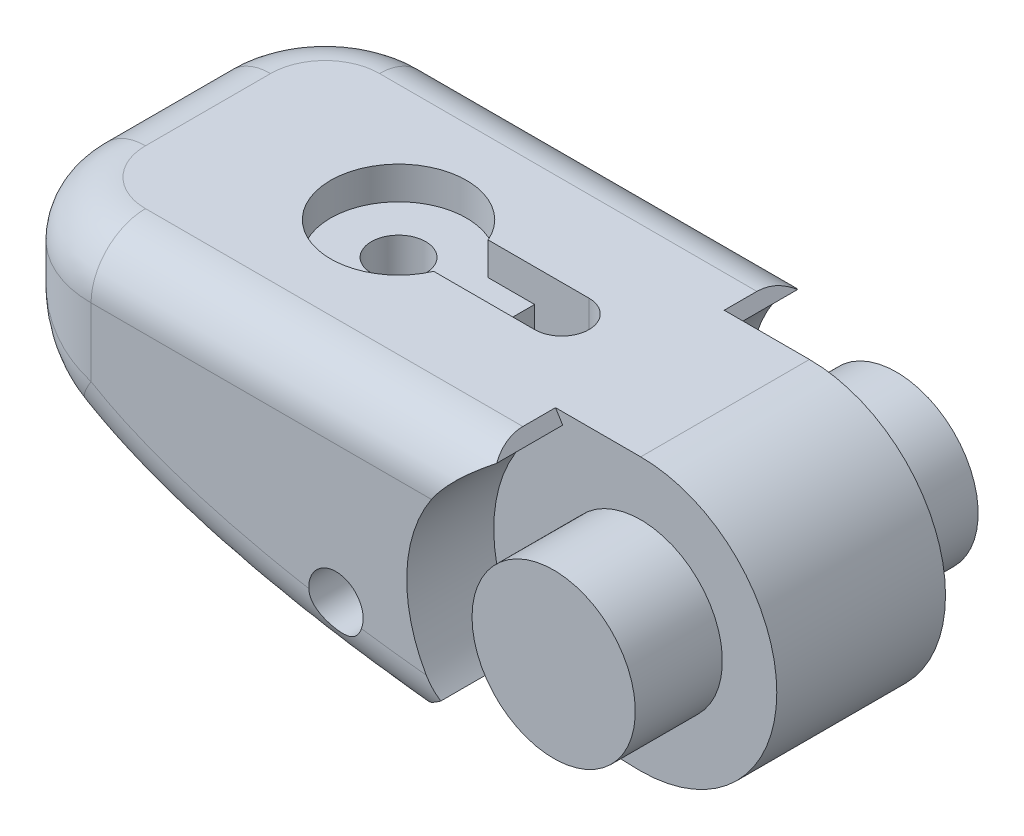
SolidWorks part; units mm, degrees
ref_plane "Front Plane" through (0, 0, 0) normal (0, 0, 1) x (1, 0, 0)
ref_plane "Top Plane" through (0, 0, 0) normal (0, 1, 0) x (1, 0, 0)
ref_plane "Right Plane" through (0, 0, 0) normal (1, 0, 0) x (0, 0, -1)
sketch "Width-Sketch" plane through (0, 0, 0) normal (0, 1, 0) x (1, 0, 0)
  line L0 (0, 0) -> (0, -2.1) construction
  line L1 (0, -2.1) -> (0, -4.2) construction
  line L2 (0, -4.2) -> (0, -6.3) construction
  line L3 (0, -6.3) -> (0, -8.4) construction
  line L4 (0, -8.4) -> (0, -10.5) construction
  dimension "D1" = 2.1
ref_plane "Centre-Plane" through (0, 0, 6.3) normal (0, 0, 1) x (1, 0, 0)
sketch "Sketch1" plane through (0, 0, 0) normal (0, 0, 1) x (1, 0, 0)
  line L0 (0, 5) -> (-21, 5)
  arc A2 (0, -5) -> (0, 5) centre (0, 0) ccw
  spline S0 degree 3 poles (-21, 5) (-23.8378, -4.4787) (-0.5767, -5.0045) (0, -5) knots 0 0 0 0 1 1 1 1
  dimension "D1" = 5
  dimension "D2" = 21
extrude "Boss-Extrude1" add sketch "Sketch1" along normal up to vertex (6.3 mm away) up to point (0, 0, 6.3)
surface "Surface-Offset1" parameters "D1"=0
sketch "Sketch15" plane through (0, 0, 0) normal (0, 0, -1) x (-1, 0, 0)
  line L0 (2.8667, 4.5763) -> (3.1321, 5)
  line L1 (0, 5) -> (21, 5) construction
  line L2 (3.1321, 5) -> (0.78, 5.3434)
  line L3 (5.8137, -4.5784) -> (4.2424, -3.341)
  line L4 (5.8137, -4.5784) -> (0.8115, -5.3387)
  arc A0 (4.2424, -3.341) -> (2.8667, 4.5763) centre (0, 0) ccw
  arc A1 (0, 5) -> (0, -5) centre (0, 0) ccw construction
  circle A2 centre (0, 0) radius 3
  arc A3 (0.78, 5.3434) -> (0.8115, -5.3387) centre (0, 0) ccw
  spline S0 degree 3 poles (21, 5) (23.8378, -4.4787) (0.5767, -5.0045) (0, -5) knots 0 0 0 0 1 1 1 1 construction
  dimension "D2" = 6
  dimension "D1" = 0.4
  dimension "D3" = 0.5
  dimension "D4" = 2
extrude "Cut-Extrude5" cut sketch "Sketch15" against normal blind 3.2
sketch "Sketch16" plane through (0, 0, 6.3) normal (0, 0, -1) x (-1, 0, 0)
  line L0 (7, 0) -> (5, 0)
  line L2 (7, 0) -> (7, -7)
  line L4 (0, -5) -> (0, -7)
  line L5 (0, -7) -> (7, -7)
  arc A1 (0, -5) -> (5, 0) centre (0, 0) ccw
  arc A2 (0, 5) -> (0, -5) centre (0, 0) ccw construction
  dimension "D1" = 2
  dimension "D2" = 2
extrude "Cut-Extrude6" cut sketch "Sketch16" along normal blind 1
sketch "Sketch17" plane through (0, 5, 0) normal (0, 1, 0) x (1, 0, 0)
  line L0 (0, -6.3) -> (-21, -6.3) construction
  line L1 (-7, -6.3) -> (-5, -6.3) construction
  line L2 (-7, -6.3) -> (-5, -6.3) construction
  line L3 (0, -6.3) -> (-21, -6.3) construction
  circle A0 centre (-6, -6.3) radius 1
  point P10 (-6, -6.3)
  dimension "D1" = 2
extrude "Cut-Extrude7" cut sketch "Sketch17" against normal through all
mirror "Mirror1" about plane through (0, 0, 6.3) normal (0, 0, 1) of bodies 117 111
sketch "Sketch18" plane through (0, 5, 0) normal (0, 1, 0) x (1, 0, 0)
  line L0 (-6, -5.3) -> (-9.7087, -5.3)
  line L1 (-6, -5.3) -> (-12, -5.3) construction
  line L2 (-6, -5.3) -> (-6, -7.3)
  line L3 (-6, -7.3) -> (-12, -7.3) construction
  line L4 (-12, -5.3) -> (-12, -7.3) construction
  line L6 (-9.7087, -7.3) -> (-6, -7.3)
  circle A0 centre (-6, -6.3) radius 1 construction
  circle A1 centre (-6, -6.3) radius 1 construction
  arc A2 (-9.7087, -5.3) -> (-9.7087, -7.3) centre (-12, -6.3) ccw
  dimension "D1" = 2.5
  dimension "D2" = 6
extrude "Cut-Extrude8" cut sketch "Sketch18" against normal blind 1.2
sketch "Sketch19" plane through (0, 3.8, 0) normal (0, 1, 0) x (1, 0, 0)
  circle A0 centre (-12, -6.3) radius 1
  arc A1 (-9.7087, -5.3) -> (-9.7087, -7.3) centre (-12, -6.3) ccw construction
  dimension "D1" = 2
extrude "Cut-Extrude9" cut sketch "Sketch19" against normal through all
sketch "Sketch20" plane through (0, 0, 6.3) normal (0, 0, 1) x (1, 0, 0)
  line L0 (-11, 3.8) -> (-13, 3.8) construction
  line L1 (-11, 3.8) -> (-13, 3.8) construction
  line L2 (-11, 3.8) -> (-11, -3.7335) construction
  line L3 (-13, 3.8) -> (-13, -3.244) construction
  line L4 (-12, -6.9171) -> (-10.5, -6.9171)
  line L5 (-10.5, -6.9171) -> (-10.5, -1.2509)
  line L6 (-10.5, 2.2) -> (-12, 2.2)
  line L8 (-12, 3.8) -> (-12, -6.9171) construction
  line L9 (-12, -6.9171) -> (-12, 2.2)
  line L10 (-13, -3.244) -> (-11, -3.244) construction
  line L11 (-10.5, -3.1019) -> (-13.5, -3.1019) construction
  line L12 (-10.5, 0.3491) -> (-8.5, 0.3491)
  line L13 (-8.5, 0.3491) -> (-8.5, -1.2509)
  line L14 (-8.5, -1.2509) -> (-10.5, -1.2509)
  line L15 (-10.5, 0.3491) -> (-10.5, 2.2)
  line L16 (-11.3066, -3.1019) -> (-11.3066, 2.2) construction
  line L17 (-8.5, -0.4509) -> (-11.3066, -0.4509) construction
  line L18 (-9.7087, 3.8) -> (-14.5, 3.8) construction
  spline S0 degree 3 poles (935.3666, 297.1527) (-1094.429, -214.5201) (1089.6933, 139.9424) (-1000.7534, -105.0065) knots -2.236466 -2.236466 -2.236466 -2.236466 3.346347 3.346347 3.346347 3.346347 only from (-21, 5) to (-5.8137, -4.5784) construction
  spline S1 degree 3 poles (-21, 5) (-22.94, -1.48) (-12.6823, -3.7758) (-5.8137, -4.5784) knots 0 0 0 0 0.683642 0.683642 0.683642 0.683642 construction
  point P15 (-12, -3.1019)
  dimension "D1" = 1.5
  dimension "D2" = 1.6
  dimension "D3" = 1.6
  dimension "D4" = 2
revolve "Cut-Revolve2" cut sketch "Sketch20" angle 360 about L9
sketch "Sketch21" plane through (0, 0.3491, 0) normal (0, -1, 0) x (1, 0, 0)
  line L0 (-7, 7.3) -> (-6, 7.3) construction
  line L1 (-8.6459, 7.3) -> (-6, 7.3)
  line L2 (-7, 5.3) -> (-6, 5.3) construction
  line L3 (-8.6459, 5.3) -> (-6, 5.3)
  line L4 (-6, 7.3) -> (-6, 5.3)
  circle A1 centre (-12, 6.3) radius 3.5
  arc A2 (-8.6459, 5.3) -> (-8.6459, 7.3) centre (-12, 6.3) ccw
  dimension "D1" = 0
extrude "Cut-Extrude10" cut sketch "Sketch21" along normal up to surface (1.6 mm away) up to face at (-12, -1.2509, 2.8)
sketch "Sketch22" plane through (0, 3.8, 0) normal (0, 1, 0) x (1, 0, 0)
  line L0 (-6, -5.3) -> (-9.7087, -5.3) construction
  line L1 (-8, -5.3) -> (-6, -5.3)
  line L2 (-8, -5.3) -> (-8, -7.3)
  line L3 (-8, -7.3) -> (-6, -7.3)
  line L4 (-6, -5.3) -> (-6, -7.3)
  line L5 (-7, -7.3) -> (-7, -5.3) construction
  line L6 (-7, -7.3) -> (-7, -5.3) construction
  dimension "D1" = 1
extrude "Cut-Extrude11" cut sketch "Sketch22" against normal through all both and the other way through all
sketch "Sketch23" plane through (0, 0, 5.3) normal (0, 0, 1) x (1, 0, 0)
  line L0 (-8, -4.284) -> (-8, -1.2509) construction
  line L1 (-8, -2.0509) -> (-8, -1.2509) construction
  line L2 (-8, -1.2509) -> (-7.2, -1.2509) construction
  line L3 (-8, -4.284) -> (-8, -1.2509) construction
  line L9 (-7.2, -1.2509) -> (-7.2, -2.0509) construction
  line L10 (-7.2, -2.0509) -> (-8, -2.0509) construction
  circle A0 centre (-8, -2.0509) radius 1
  dimension "D1" = 2
  dimension "D2" = 0.8
extrude "Cut-Extrude12" cut sketch "Sketch23" against normal through all both and the other way through all
sketch "Sketch24" plane through (0, 5, 0) normal (0, 1, 0) x (1, 0, 0)
  line L0 (-21, -8.6) -> (-21, -4)
  line L1 (-17, -12.6) -> (-29.6, -12.6)
  line L2 (-29.6, -12.6) -> (-29.6, 0)
  line L3 (-29.6, 0) -> (-17, 0)
  line L4 (-21, -12.6) -> (-21, 0) construction
  line L5 (-3.1321, 0) -> (-21, 0) construction
  line L6 (-3.1321, -12.6) -> (-21, -12.6) construction
  arc A0 (-21, -4) -> (-17, 0) centre (-17, -4) cw
  arc A1 (-21, -8.6) -> (-17, -12.6) centre (-17, -8.6) ccw
  dimension "D2" = 4
extrude "Cut-Extrude13" cut sketch "Sketch24" against normal through all
fillet "Fillet1" radius 2 10 edges at (-10.066, 5, 0) (-19.8284, 5, 1.1716) (-21, 5, 6.3) (-19.8284, 5, 11.4284) (-10.066, 5, 12.6) (-20.5835, 1.1453, 10.3773) (-21, 2.0203, 6.3) (-20.7522, 1.4451, 2.6141)
equation "\"Ligament\"=2"
equation "\"Clearance\"=0.4"
equation "\"D1@Sketch15\"=\"Clearance\""
equation "\"D1@Sketch17\"=\"Ligament\""
equation "\"D1@Sketch16\"=\"Ligament\""
equation "\"D1@Cut-Extrude6\"=\"Ligament\"/2"
equation "\"D1@Cut-Extrude8\"=\"Ligament\"/2"
equation "\"Trim\"=0.5"
equation "\"D3@Sketch15\"=\"Trim\""
equation "\"D4@Sketch15\"=\"Trim\"*4"
equation "\"D2@Sketch23\"=\"Clearance\"*2"
equation "\"D1@Width-Sketch\"    = \"Ligament\"*1.05"
